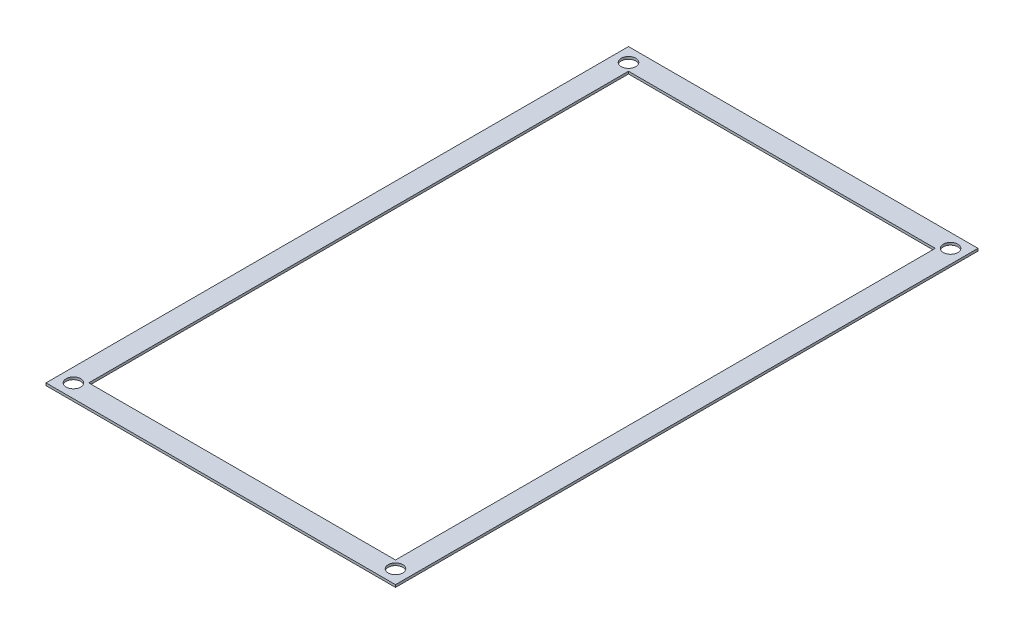
SolidWorks part; units mm, degrees
material "Rubber"
ref_plane "Front Plane" through (0, 0, 0) normal (0, 0, 1) x (1, 0, 0)
ref_plane "Top Plane" through (0, 0, 0) normal (0, 1, 0) x (1, 0, 0)
ref_plane "Right Plane" through (0, 0, 0) normal (1, 0, 0) x (0, 0, -1)
sketch "Sketch3" plane through (0, 0, 0) normal (0, 1, 0) x (1, 0, 0)
  line L1 (-18, 26) -> (-18, 35.8093)
  line L2 (-18, 35.8093) -> (-8.1907, 35.8093)
  line L4 (0, 22.5721) -> (0, 0) construction
  line L6 (-17, 5.8093) -> (17, 5.8093) construction
  line L8 (18, 26) -> (18, -14.3815)
  line L9 (-18, 35.8093) -> (-15.1716, 32.9808) construction
  line L11 (-18, 35.8093) -> (-18, 26)
  line L12 (-8.1907, 35.8093) -> (-18, 35.8093)
  line L13 (18, 35.8093) -> (15.1716, 32.9808) construction
  line L14 (8.1907, 35.8093) -> (18, 35.8093)
  line L15 (18, 35.8093) -> (18, 26)
  line L16 (18, 35.8093) -> (8.1907, 35.8093)
  line L17 (18, 26) -> (18, 35.8093)
  line L18 (18, -24.1907) -> (15.1716, -21.3623) construction
  line L19 (-18, -24.1907) -> (-15.1716, -21.3623) construction
  line L20 (18, -14.3815) -> (18, -24.1907)
  line L21 (18, -24.1907) -> (8.1907, -24.1907)
  line L22 (18, -24.1907) -> (18, -14.3815)
  line L23 (8.1907, -24.1907) -> (18, -24.1907)
  line L24 (-8.1907, -24.1907) -> (-18, -24.1907)
  line L25 (-18, -24.1907) -> (-18, -14.3815)
  line L26 (-18, -24.1907) -> (-8.1907, -24.1907)
  line L27 (-18, -14.3815) -> (-18, -24.1907)
  line L31 (8.1907, -24.1907) -> (-8.1907, -24.1907)
  line L32 (-18, -14.3815) -> (-18, 26)
  line L33 (-8.1907, 35.8093) -> (8.1907, 35.8093)
  circle A1 centre (-16.5858, 34.3951) radius 0.75
  circle A6 centre (16.5858, 34.3951) radius 0.75
  circle A7 centre (16.5858, -22.7765) radius 0.75
  circle A10 centre (-16.5858, -22.7765) radius 0.75
  point P2 (0, 0)
  point P3 (-17, 5.8093)
  point P11 (0, 30)
  dimension "D2" = 1.5
  dimension "D1" = 1.4142
  dimension "D3" = 30
  dimension "D4" = 18
  dimension "D5" = 35.8093
extrude "Boss-Extrude1" add sketch "Sketch3" along normal blind 0.25 contours L33 L2 L1 L32 L25 L24 L31 L21 L20 L8 L15 L14 A6 A1 A7 A10 region at (0, 0, -5.8093)
sketch "Sketch4" plane through (0, 0.25, 0) normal (0, 1, 0) x (1, 0, 0)
  line L0 (-18, -24.1907) -> (-18, 35.8093) construction
  line L1 (-18, 35.8093) -> (18, 35.8093) construction
  line L2 (18, 35.8093) -> (18, -24.1907) construction
  line L3 (15.8, -21.9907) -> (-15.8, -21.9907)
  line L4 (15.8, -21.9907) -> (15.8, 33.6093)
  line L5 (15.8, 33.6093) -> (-15.8, 33.6093)
  line L6 (-15.8, -21.9907) -> (-15.8, 33.6093)
  line L7 (15.8, -21.9907) -> (-15.8, 33.6093) construction
  line L8 (15.8, 33.6093) -> (-15.8, -21.9907) construction
  line L9 (18, -24.1907) -> (-18, -24.1907) construction
  point P0 (-18, 5.8093)
  point P1 (0, 35.8093)
  point P4 (0, 5.8093)
  dimension "D1" = 2.2
  dimension "D2" = 2.2
  dimension "D3" = 2.2
  dimension "D4" = 2.2
extrude "Cut-Extrude1" cut sketch "Sketch4" against normal blind 10
